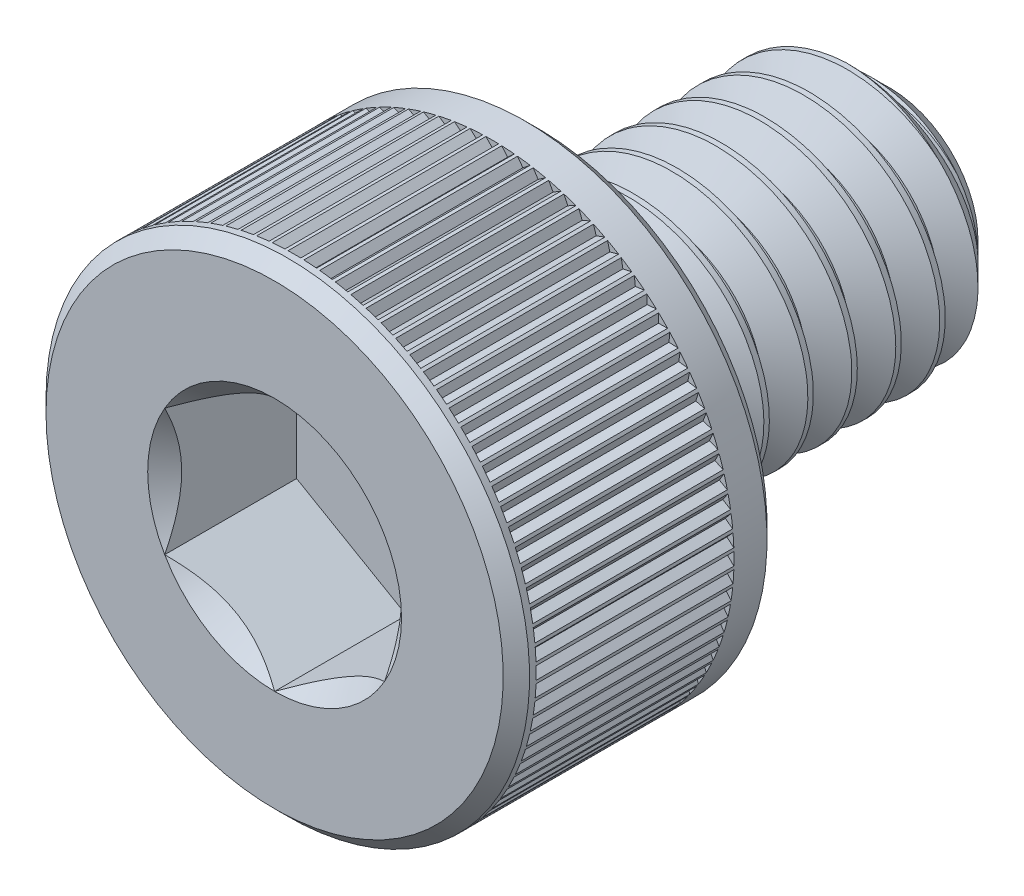
SolidWorks part; units mm, degrees
ref_plane "Front Plane" through (0, 0, 0) normal (0, 0, 1) x (1, 0, 0)
ref_plane "Top Plane" through (0, 0, 0) normal (0, 1, 0) x (1, 0, 0)
ref_plane "Right Plane" through (0, 0, 0) normal (1, 0, 0) x (0, 0, -1)
sketch "Sketch1" plane through (0, 0, 0) normal (1, 0, 0) x (0, 0, -1)
  line L0 (-3.5, 0) -> (3.5, 0) construction
  line L1 (3.5, 0) -> (3.5, 1) construction
  line L2 (3.5, 1) -> (3, 1.5) construction
  line L3 (3, 1.5) -> (-0.5, 1.5) construction
  line L5 (-0.5, 1.5) -> (-0.5, 2.75) construction
  line L6 (-0.5, 2.75) -> (-3.5, 2.75) construction
  line L7 (-3.5, 2.75) -> (-3.5, 0) construction
  line L8 (3.5, 1) -> (3.5, 1.5) construction
  line L9 (3.4687, 1.5541) -> (3.7188, 1.1211) construction
  line L10 (3.7188, 1.1211) -> (3.9688, 1.5541) construction
  line L11 (3.9688, 1.5541) -> (3.4687, 1.5541) construction
  line L12 (3.7188, 1.5541) -> (3.7188, 1.5) construction
  line L13 (3.7188, 1.1211) -> (3.7188, 1.1752) construction
  line L14 (3.6875, 1.1752) -> (3.75, 1.1752) construction
  line L15 (3.5, 1.5) -> (3.9375, 1.5) construction
  line L16 (3.4844, 1.5271) -> (3.9531, 1.5271) construction
  line L17 (3.5, 0) -> (3.5, -1.5) construction
  line L18 (-0.65, 2.75) -> (-0.5, 2.6) construction
  line L19 (-3.35, 2.75) -> (-3.5, 2.6) construction
  point P0 (-3.5, 1.25)
  point P3 (1.75, 1.5)
  point P4 (0, 0)
  point P22 (3.7188, 1.1752)
  point P24 (-0.5, 1.5)
  point P25 (3.7188, 1.5)
  point P28 (3.7188, 1.5271)
  point P29 (1.75, -1.5)
  point P31 (-2, 2.75)
  point P37 (-1.025, 2.75)
  point P38 (-3.275, 2.75)
  point P41 (-2, 0)
  dimension "head height" = 3
  dimension "D1" = 45
  dimension "Head Diameter" = 5.5
  dimension "Thread Size" = 3
  dimension "drive size" = 2.5
  dimension "Thread Pitch" = 0.5
  dimension "D2" = 0.0625
  dimension "D3" = 0.5
  dimension "D4" = 1.75
  dimension "D7" = 0.15
  dimension "D8" = 0.15
  dimension "D9" = 0.15
  dimension "D10" = 0.075
  dimension "D11" = 0.375
  dimension "length" = 4
  dimension "Drive Depth" = 1.5
sketch "Sketch2" plane through (0, 0, 0) normal (1, 0, 0) x (0, 0, -1)
  line L1 (-3.35, 2.75) -> (-0.65, 2.75)
  line L4 (3, 1.5) -> (3.5, 1)
  line L5 (3.5, 1) -> (3.5, 0)
  line L6 (-0.65, 2.75) -> (-0.5, 2.6) construction
  line L7 (3.5, 0) -> (-3.5, 0)
  line L8 (-3.35, 2.75) -> (-3.5, 2.6) construction
  line L9 (-0.65, 2.75) -> (-0.5, 2.6)
  line L10 (-3.35, 2.75) -> (-3.5, 2.6)
  line L11 (-3.5, 2.6) -> (-3.5, 0)
  line L12 (-0.5, 2.6) -> (-0.5, 1.5)
  line L13 (-0.5, 1.5) -> (3, 1.5)
revolve "Revolve1" add sketch "Sketch2" angle 360 about L7
sketch "Sketch3" plane through (0, 0, 3.5) normal (0, 0, 1) x (1, 0, 0)
  line L1 (0, 1.4434) -> (-1.25, 0.7217)
  line L2 (-1.25, 0.7217) -> (-1.25, -0.7217)
  line L3 (-1.25, -0.7217) -> (0, -1.4434)
  line L4 (0, -1.4434) -> (1.25, -0.7217)
  line L5 (1.25, -0.7217) -> (1.25, 0.7217)
  line L6 (1.25, 0.7217) -> (0, 1.4434)
  circle A0 centre (0, 0) radius 1.25 construction
  dimension "D1" = 2.5
extrude "Cut-Extrude1" cut sketch "Sketch3" against normal up to vertex (1.5 mm away) up to point (0, 0, 2)
sketch "Sketch4" plane through (0, 0, 3.5) normal (0, 0, 1) x (1, 0, 0)
  circle A0 centre (0, 0) radius 1.4434
extrude "Cut-Extrude2" cut sketch "Sketch4" against normal blind 0.5 draft 45
ref_plane "Plane1" through (0, 0, 0.5) normal (0, 0, 1) x (1, 0, 0)
split "Split1" bodies to split 106 resulting bodies 108 115 split by face at (-2.6, 0, 0.5)
sketch "Sketch6" plane through (0, 0, -3.5) normal (0, 0, -1) x (-1, 0, 0)
  circle A0 centre (0, 0) radius 1.5
curve "Helix/Spiral1" pitch 0.5 height 4.5 radius 1.5 centre (0, 0, -3.5) axis (0, 0, 1) start towards (0, 1, 0)
sketch "Sketch7" plane through (0, 0, 0) normal (1, 0, 0) x (0, 0, -1)
  line L0 (3.4844, 1.5271) -> (3.9531, 1.5271)
  line L1 (3.9531, 1.5271) -> (3.75, 1.1752)
  line L2 (3.75, 1.1752) -> (3.6875, 1.1752)
  line L3 (3.6875, 1.1752) -> (3.4844, 1.5271)
sweep "Cut-Sweep1" cut profiles "Sketch7" path "Helix/Spiral1" align with end faces yes
sketch "Sketch8" plane through (0, 0, 0.5) normal (0, 0, -1) x (-1, 0, 0)
  circle A0 centre (0, 0) radius 1.5
extrude "Boss-Extrude1" add sketch "Sketch8" along normal through all draft 45
ref_plane "Plane2" through (0, 0, 2) normal (0, 0, 1) x (1, 0, 0)
sketch "Sketch9" plane through (0, 0, 2) normal (0, 0, 1) x (1, 0, 0)
  line L0 (0, 2.6744) -> (0.072, 2.7491)
  line L1 (0, 2.6744) -> (-0.072, 2.7491)
  line L2 (0, 2.75) -> (0, 0) construction
  line L3 (-0.072, 2.7491) -> (0, 0) construction
  line L4 (0, 0) -> (0.072, 2.7491) construction
  arc A0 (0.072, 2.7491) -> (-0.072, 2.7491) centre (0, 0) ccw
  circle A1 centre (0, 0) radius 2.6744 construction
  dimension "D1" = 5.5
  dimension "D2" = 5.3487
  dimension "D3" = 3
extrude "Cut-Extrude4" cut sketch "Sketch9" against normal up to vertex (0.975 mm away) and the other way up to vertex (1.275 mm away) up to point (0, 2.75, 1.025) other way up to point (0, 2.75, 3.275)
pattern_circular "CirPattern2" count 96 over 360 about axis through (0, 0, 3.5) along (0, 0, -1) of "Cut-Extrude4"
equation "\"D2@Sketch1\" = \"Thread Pitch@Sketch1\" / 8"
equation "\"D3@Sketch1\" = \"Thread Pitch@Sketch1\""
equation "\"D3@Helix/Spiral1\" = \"length@Sketch1\" + \"Thread Pitch@Sketch1\""
equation "\"D4@Helix/Spiral1\" = \"Thread Pitch@Sketch1\""
equation "\"D4@Sketch1\" = \"Thread Pitch@Sketch1\" * 3.5"
equation "\"D7@Sketch1\"=\"head height@Sketch1\"*.05"
equation "\"D8@Sketch1\"=\"D7@Sketch1\""
equation "\"D9@Sketch1\"=\"D7@Sketch1\""
equation "\"D10@Sketch1\"=\"D7@Sketch1\"/2"
equation "\"D11@Sketch1\"=\"D10@Sketch1\"*5"
equation "\"D1@CirPattern2\"=( 360 / \"D3@Sketch9\" )*0.8"
equation "\"D1@Sketch3\" = \"drive size@Sketch1\""
equation "\"D2@Sketch9\"=\"Head Diameter@Sketch1\" * 0.9725"
